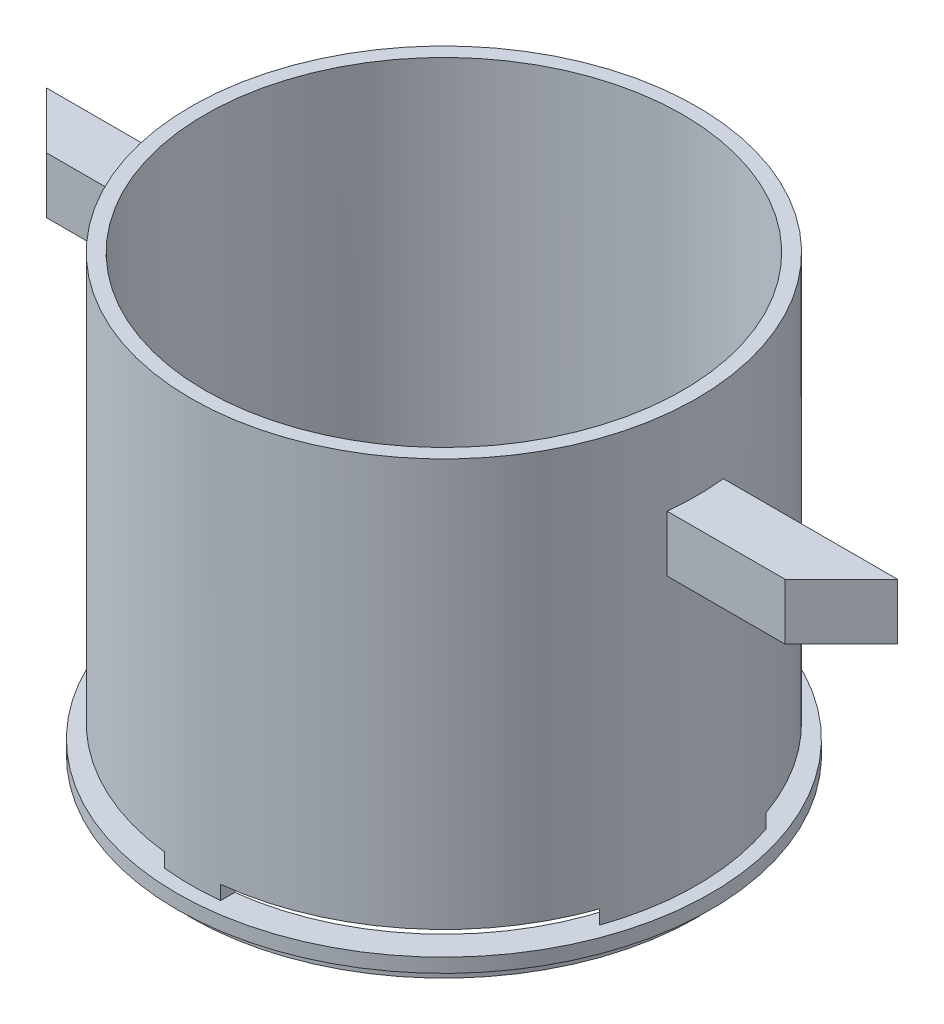
SolidWorks part; units mm, degrees
ref_plane "Front Plane" through (0, 0, 0) normal (0, 0, 1) x (1, 0, 0)
ref_plane "Top Plane" through (0, 0, 0) normal (0, 1, 0) x (1, 0, 0)
ref_plane "Right Plane" through (0, 0, 0) normal (1, 0, 0) x (0, 0, -1)
sketch "Sketch1" plane through (0, 0, 0) normal (0, 1, 0) x (1, 0, 0)
  circle A0 centre (0, 0) radius 57.15
  dimension "D2" = 114.3
extrude "Boss-Extrude1" add sketch "Sketch1" along normal blind 101.6
sketch "Sketch2" plane through (0, 101.6, 0) normal (0, 1, 0) x (1, 0, 0)
  circle A0 centre (0, 0) radius 53.975
  circle A1 centre (0, 0) radius 57.15 construction
  dimension "D2" = 3.175
extrude "Cut-Extrude1" cut sketch "Sketch2" against normal through all
sketch "Sketch6" plane through (0, 0, 0) normal (0, 0, 1) x (1, 0, 0)
  line L0 (-57.15, 101.6) -> (-57.15, 0) construction
  line L1 (-53.975, 9.525) -> (-6.35, 9.525)
  line L2 (-53.975, 9.525) -> (-53.975, 6.35)
  line L3 (-53.975, 6.35) -> (-6.35, 6.35)
  line L7 (-53.975, 0) -> (53.975, 0) construction
  line L8 (-6.35, 9.525) -> (-6.35, 6.35)
  line L9 (0, 0) -> (0, 21.9448) construction
  line L10 (6.35, 9.525) -> (6.35, 6.35)
  line L11 (53.975, 6.35) -> (6.35, 6.35)
  line L12 (53.975, 9.525) -> (6.35, 9.525)
  line L13 (53.975, 9.525) -> (53.975, 6.35)
  dimension "D1" = 6.35
  dimension "D2" = 3.175
  dimension "D3" = 3.175
  dimension "D4" = 6.35
extrude "Cut-Extrude4" cut sketch "Sketch6" against normal through all both and the other way through all
ref_plane "Plane1" through (0, 69.85, 0) normal (0, 1, 0) x (1, 0, 0)
sketch "Sketch9" plane through (0, 69.85, 0) normal (0, 1, 0) x (1, 0, 0)
  line L0 (96.1526, 6.35) -> (83.4526, -6.35)
  line L1 (-83.4526, -6.35) -> (-53.6002, -6.35)
  line L3 (-96.1526, 6.35) -> (-53.6002, 6.35)
  line L5 (-96.1526, -6.35) -> (96.1526, 6.35) construction
  line L6 (-96.1526, 6.35) -> (96.1526, -6.35) construction
  line L7 (-96.1526, 6.35) -> (-83.4526, -6.35)
  line L8 (53.6002, 6.35) -> (96.1526, 6.35)
  line L9 (53.6002, -6.35) -> (83.4526, -6.35)
  circle A0 centre (0, 0) radius 53.975 construction
  arc A1 (-53.6002, 6.35) -> (-53.6002, -6.35) centre (0, 0) ccw
  arc A2 (53.6002, -6.35) -> (53.6002, 6.35) centre (0, 0) ccw
  point P0 (0, 0)
  dimension "D1" = 192.3051
  dimension "D2" = 45
  dimension "D3" = 45
  dimension "D4" = 12.7
extrude "Boss-Extrude6" add sketch "Sketch9" along normal blind 12.7
sketch "Sketch10" plane through (0, 0, 0) normal (0, 1, 0) x (1, 0, 0)
  circle A0 centre (0, 0) radius 60.325
  circle A1 centre (0, 0) radius 57.15 construction
  circle A2 centre (0, 0) radius 57.15
  dimension "D1" = 120.65
extrude "Boss-Extrude7" add sketch "Sketch10" along normal blind 3.175 from offset 3.175
